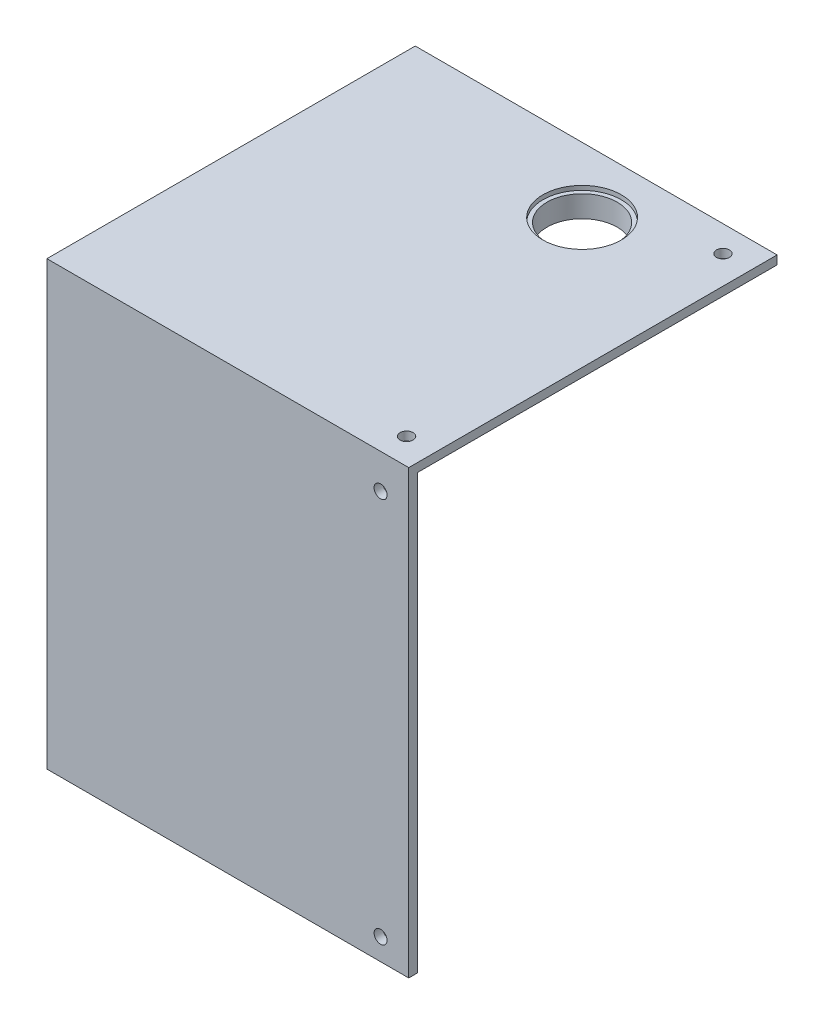
SolidWorks part; units mm, degrees
ref_plane "Front Plane" through (0, 0, 0) normal (0, 0, 1) x (1, 0, 0)
ref_plane "Top Plane" through (0, 0, 0) normal (0, 1, 0) x (1, 0, 0)
ref_plane "Right Plane" through (0, 0, 0) normal (1, 0, 0) x (0, 0, -1)
sketch "Sketch1" plane through (0, 0, 0) normal (0, 1, 0) x (1, 0, 0)
  line L1 (-41.75, -42.5) -> (41.75, -42.5)
  line L2 (-41.75, -42.5) -> (-41.75, 42.5)
  line L3 (-41.75, 42.5) -> (41.75, 42.5)
  line L4 (41.75, -42.5) -> (41.75, 42.5)
  line L5 (0, 42.5) -> (0, -42.5) construction
  line L6 (-41.75, 0) -> (41.75, 0) construction
  point P0 (0, 0)
  dimension "D1" = 83.5
  dimension "D2" = 85
extrude "Boss-Extrude1" add sketch "Sketch1" along normal blind 2
sketch "Sketch2" plane through (0, 0, 0) normal (0, -1, 0) x (-1, 0, 0)
  line L0 (-41.75, -42.5) -> (-41.75, 42.5) construction
  line L2 (41.75, -42.5) -> (-41.75, -42.5)
  line L3 (41.75, -42.5) -> (41.75, -40.5)
  line L4 (41.75, -40.5) -> (-41.75, -40.5)
  line L5 (-41.75, -42.5) -> (-41.75, -40.5)
  dimension "D1" = 2
extrude "Boss-Extrude2" add sketch "Sketch2" along normal blind 100
sketch "Sketch3" plane through (0, 0, 0) normal (0, -1, 0) x (-1, 0, 0)
  line L0 (-41.75, 42.5) -> (41.75, 42.5) construction
  line L1 (-41.75, -40.5) -> (-41.75, 42.5) construction
  circle A0 centre (-11.75, 27.5) radius 8.1
  circle A1 centre (-11.75, 27.5) radius 10.6
  dimension "D3" = 16.2
  dimension "D1" = 15
  dimension "D2" = 30
  dimension "D4" = 2.5
extrude "Boss-Extrude3" add sketch "Sketch3" along normal blind 4 contours A0 | A1 A0 region at (11.75, 0, -27.5) region at (22.0502, 0, -27.5)
extrude "Cut-Extrude3" cut sketch "Sketch3<3>" against normal through all both and the other way through all contours A0 region at (11.75, 0, -27.5)
sketch "Sketch3<3>" plane through (0, 0, 0) normal (0, -1, 0) x (-1, 0, 0) same geometry as "Sketch3"
sketch "Sketch4" plane through (0, 2, 0) normal (0, 1, 0) x (1, 0, 0)
  circle A0 centre (11.75, 27.5) radius 9.05
  dimension "D1" = 18.1
extrude "Cut-Extrude4" cut sketch "Sketch4" against normal blind 1
sketch "Sketch5" plane through (0, 0, 42.5) normal (0, 0, 1) x (1, 0, 0)
  line L0 (41.75, 2) -> (41.75, -100) construction
  line L1 (41.75, -100) -> (-41.75, -100) construction
  line L2 (-41.75, 2) -> (41.75, 2) construction
  circle A0 centre (35.25, -95) radius 1.5
  circle A1 centre (35.25, -6) radius 1.5
  dimension "D5" = 3
  dimension "D1" = 6.5
  dimension "D2" = 5
  dimension "D3" = 6.5
  dimension "D4" = 8
extrude "Cut-Extrude5" cut sketch "Sketch5" against normal up to next
sketch "Sketch6" plane through (0, 2, 0) normal (0, 1, 0) x (1, 0, 0)
  line L0 (41.75, -42.5) -> (41.75, 42.5) construction
  line L1 (-41.75, -42.5) -> (41.75, -42.5) construction
  line L2 (41.75, 42.5) -> (-41.75, 42.5) construction
  circle A0 centre (35.25, -36.5) radius 1.5
  circle A1 centre (35.25, 36.5) radius 1.5
  dimension "D5" = 3
  dimension "D1" = 6.5
  dimension "D2" = 6
  dimension "D3" = 6
  dimension "D4" = 6.5
extrude "Cut-Extrude6" cut sketch "Sketch6" against normal up to next
